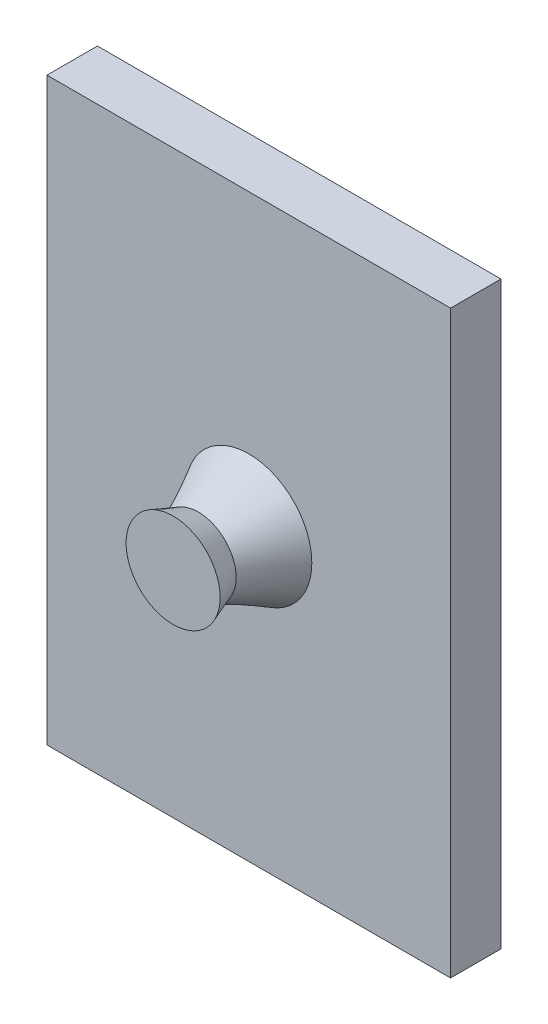
SolidWorks part; units mm, degrees
ref_plane "Front Plane" through (0, 0, 0) normal (0, 0, 1) x (1, 0, 0)
ref_plane "Top Plane" through (0, 0, 0) normal (0, 1, 0) x (1, 0, 0)
ref_plane "Right Plane" through (0, 0, 0) normal (1, 0, 0) x (0, 0, -1)
sketch "Sketch1" plane through (0, 0, 0) normal (0, 0, 1) x (1, 0, 0)
  line L1 (0, 0) -> (16, 0)
  line L2 (0, 0) -> (0, 23)
  line L3 (0, 23) -> (16, 23)
  line L4 (16, 0) -> (16, 23)
  dimension "D1" = 16
  dimension "D2" = 23
extrude "Boss-Extrude1" add sketch "Sketch1" along normal blind 2
sketch "Sketch2" plane through (0, 0, 2) normal (0, 0, 1) x (1, 0, 0)
  line L0 (16, 0) -> (16, 23) construction
  line L1 (0, 0) -> (16, 0) construction
  circle A0 centre (8, 11.5) radius 2.5
  point P2 (0, 0)
  point P5 (16, 11.5)
  point P6 (5.3489, 11.5)
  point P9 (8, 0)
  dimension "D1" = 5
ref_plane "Plane1" through (0, 0, 4) normal (0, 0, 1) x (1, 0, 0)
sketch "Sketch4" plane through (0, 0, 4) normal (0, 0, 1) x (1, 0, 0)
  circle A0 centre (8, 11.5) radius 1.5
  dimension "D1" = 3
loft "Loft1" add profiles "Sketch2", "Sketch4" connector at (10.5, 11.5, 2) connector at (9.3822, 10.9173, 4)
sketch "Sketch6" plane through (0, 0, 4) normal (0, 0, 1) x (1, 0, 0)
  circle A0 centre (8, 11.5) radius 1.5 construction
  circle A1 centre (8, 11.5) radius 1.5
extrude "Boss-Extrude3" add sketch "Sketch6" along normal blind 1 draft 20 draft outward yes
